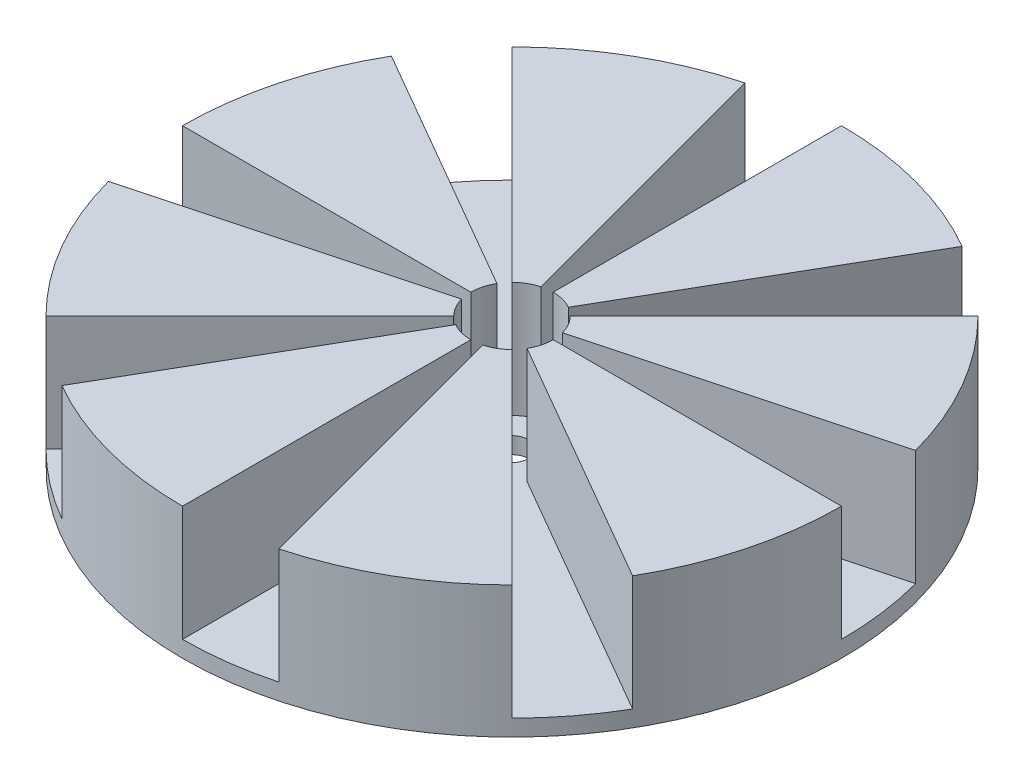
SolidWorks part; units mm, degrees
ref_plane "Front Plane" through (0, 0, 0) normal (0, 0, 1) x (1, 0, 0)
ref_plane "Top Plane" through (0, 0, 0) normal (0, 1, 0) x (1, 0, 0)
ref_plane "Right Plane" through (0, 0, 0) normal (1, 0, 0) x (0, 0, -1)
sketch "Sketch1" plane through (0, 0, 0) normal (0, 1, 0) x (1, 0, 0)
  circle A0 centre (0, 0) radius 20
  dimension "D1" = 40
extrude "First Extrude for Rubber Piece" add sketch "Sketch1" along normal blind 1
sketch "Sketch2" plane through (0, 1, 0) normal (0, 1, 0) x (1, 0, 0)
  line L0 (0, 2.5) -> (0, 20)
  line L1 (-2.5, 0) -> (-20, 0)
  line L2 (2.5, 0) -> (20, 0)
  line L3 (0, -2.5) -> (0, -20)
  line L4 (-0.647, 2.4148) -> (-5.1764, 19.3185)
  line L5 (0.647, -2.4148) -> (5.1764, -19.3185)
  line L6 (-10, 17.3205) -> (-1.25, 2.1651) construction
  line L7 (-14.1421, 14.1421) -> (-1.7678, 1.7678)
  line L8 (-17.3205, 10) -> (-2.1651, 1.25)
  line L9 (-19.3185, 5.1764) -> (-2.4148, 0.647) construction
  line L10 (19.3185, 5.1764) -> (2.4148, 0.647)
  line L11 (17.3205, 10) -> (2.1651, 1.25) construction
  line L12 (14.1421, 14.1421) -> (1.7678, 1.7678)
  line L13 (10, 17.3205) -> (1.25, 2.1651)
  line L14 (0.647, 2.4148) -> (5.1764, 19.3185) construction
  line L15 (-0.647, -2.4148) -> (-5.1764, -19.3185) construction
  line L16 (-1.7678, -1.7678) -> (-14.1421, -14.1421)
  line L17 (-2.1651, -1.25) -> (-17.3205, -10) construction
  line L18 (-2.4148, -0.647) -> (-19.3185, -5.1764)
  line L19 (2.4148, -0.647) -> (19.3185, -5.1764) construction
  line L20 (2.1651, -1.25) -> (17.3205, -10)
  line L21 (1.7678, -1.7678) -> (14.1421, -14.1421)
  line L22 (1.25, -2.1651) -> (10, -17.3205) construction
  line L23 (-1.25, -2.1651) -> (-10, -17.3205)
  circle A0 centre (0, 0) radius 20 construction
  circle A1 centre (0, 0) radius 2.5
  circle M6 centre (0, 0) radius 20
  dimension "D11" = 5
  dimension "D1" = 15
  dimension "D2" = 15
  dimension "D3" = 0
  dimension "D4" = 15
  dimension "D5" = 0
  dimension "D6" = 15
  dimension "D7" = 0
  dimension "D8" = 15
  dimension "D9" = 0
  dimension "D10" = 15
extrude "Second Extrude for Rubber Piece" add sketch "Sketch2" along normal blind 7 contours A1 L8 L1 M6 | A1 L4 L7 M6 | A1 L13 L0 M6 | A1 L10 L12 M6 | A1 L20 L2 M6 | A1 L5 L21 M6 | A1 L23 L3 M6 | A1 L18 L16 M6 region at (3.459, 1, -12.9092) region at (-6.6823, 1, -11.5741) region at (11.5741, 1, -6.6823) region at (-12.9092, 1, -3.459) region at (12.9092, 1, 3.459) region at (-11.5741, 1, 6.6823) region at (6.6823, 1, 11.5741) region at (-3.459, 1, 12.9092)
sketch "Sketch3" plane through (0, 1, 0) normal (0, 1, 0) x (1, 0, 0)
  circle A0 centre (0, 0) radius 1
  dimension "D1" = 2
extrude "Hole for Screw (Rubber)" cut sketch "Sketch3" along normal blind 23 and the other way blind 15
